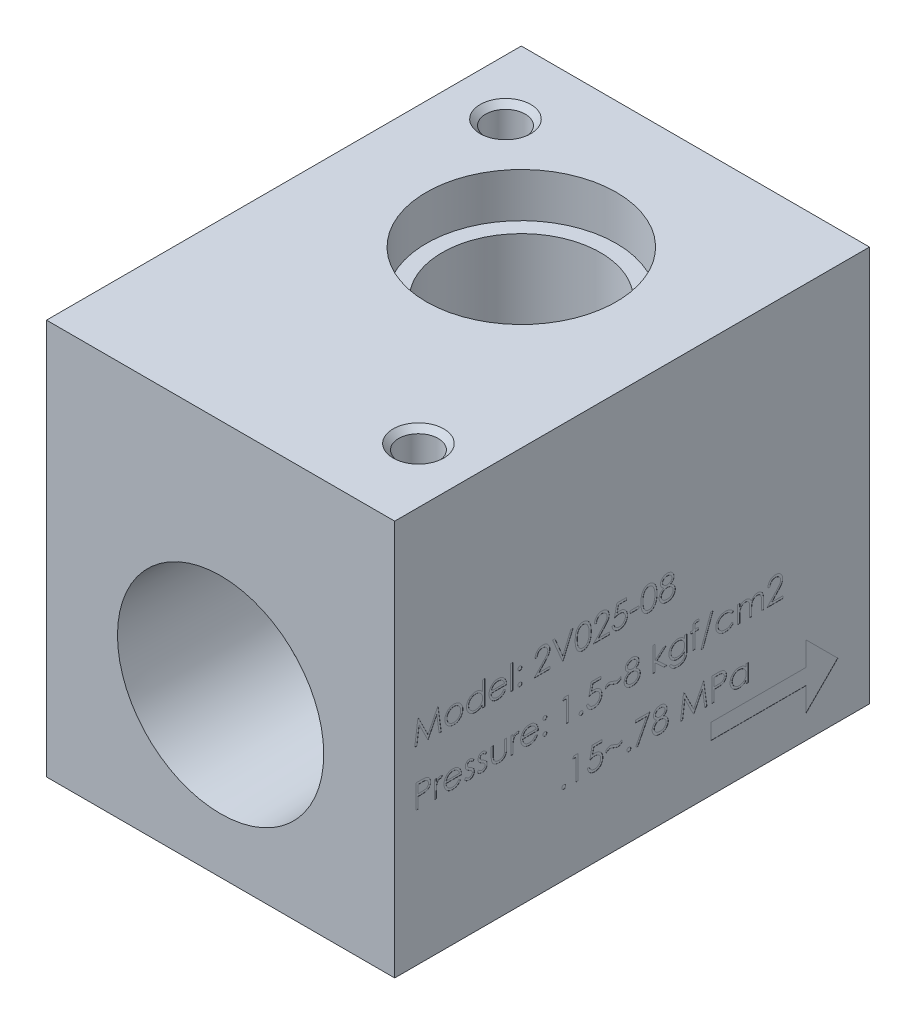
SolidWorks part; units mm, degrees
material "6061-T6 (SS)"
ref_plane "Front Plane" through (0, 0, 0) normal (0, 0, 1) x (1, 0, 0)
ref_plane "Top Plane" through (0, 0, 0) normal (0, 1, 0) x (1, 0, 0)
ref_plane "Right Plane" through (0, 0, 0) normal (1, 0, 0) x (0, 0, -1)
sketch "BaseS" plane through (0, 0, 0) normal (0, 1, 0) x (1, 0, 0)
  line L1 (-11, 15) -> (11, 15)
  line L2 (-11, 15) -> (-11, -15)
  line L3 (-11, -15) -> (11, -15)
  line L4 (11, 15) -> (11, -15)
  line L5 (-11, 15) -> (11, -15) construction
  line L6 (-11, -15) -> (11, 15) construction
  point P0 (0, 0)
  dimension "D1" = 22
  dimension "D2" = 30
extrude "BASE" add sketch "BaseS" along normal blind 25
sketch "TopBoreS" plane through (0, 25, 0) normal (0, 1, 0) x (1, 0, 0)
  line L0 (0, 15) -> (0, 4) construction
  line L2 (11, 15) -> (-11, 15) construction
  circle A0 centre (0, 4) radius 6
  dimension "D2" = 12
  dimension "D1" = 11
extrude "TOP BORE" cut sketch "TopBoreS" against normal blind 2.8
sketch "TopDeepBoreS" plane through (0, 22.2, 0) normal (0, 1, 0) x (1, 0, 0)
  circle A0 centre (0, 4) radius 5
  circle A1 centre (0, 4) radius 6 construction
  dimension "D1" = 1
  dimension "D2" = 10
extrude "TOP DEEP BORE" cut sketch "TopDeepBoreS" against normal offset from surface (6.2 mm away) 9 up to face at (0, 25, 2)
hole_wizard "M3x0.5 Tapped Hole1" positions "Sketch4" profile "Sketch5" tap size "M3x0.5" standard "ANSI Metric"
sketch "Sketch4" plane through (0, 25, 0) normal (0, 1, 0) x (1, 0, 0)
  line L0 (-11, -15) -> (11, -15) construction
  line L1 (11, -15) -> (11, 15) construction
  line L2 (-11, 15) -> (-11, -15) construction
  line L3 (11, 15) -> (-11, 15) construction
  point P0 (7.5, -10)
  point P7 (-7.5, 10.5)
  dimension "D1" = 5
  dimension "D2" = 3.5
  dimension "D3" = 3.5
  dimension "D4" = 4.5
  dimension "D5" = 15
  dimension "D6" = 20.5
sketch "Sketch5" plane through (7.5, 25, 10) normal (1, 0, 0) x (0, 0, 1)
  line L0 (0, 0) -> (0, 6.7511)
  line L1 (0, 6.7511) -> (1.25, 6)
  line L2 (1.25, 6) -> (1.25, 0.35)
  line L3 (1.25, 0.35) -> (1.6, 0)
  line L5 (1.6, 0) -> (0, 0)
  line L6 (-1.25, 0.35) -> (-1.6, 0) construction
  line L10 (0, 6.7511) -> (-1.25, 6) construction
  line L11 (0, -6.35) -> (0, 107.95) construction
  dimension "Tap Drill Dia." = 2.5
  dimension "Tap Drill Depth" = 6
  dimension "Near C'Sink Dia." = 3.2
  dimension "Near C'Sink Angle" = 90
  dimension "Drill Angle" = 118
cosmetic thread "Hole Thread1" parameters "D1"=4, "D2"=3
cosmetic thread "Hole Thread2" parameters "D1"=4, "D2"=3
hole_wizard "M3x0.5 Tapped Hole2" positions "Sketch12" profile "Sketch13" tap size "M3x0.5" standard "ANSI Metric"
sketch "Sketch12" plane through (0, 0, 0) normal (0, -1, 0) x (-1, 0, 0)
  line L1 (11, 15) -> (11, -15) construction
  line L2 (11, -15) -> (-11, -15) construction
  point P0 (7.5, -10.5)
  dimension "D1" = 4.5
  dimension "D2" = 3.5
sketch "Sketch13" plane through (-7.5, 0, 10.5) normal (1, 0, 0) x (0, 0, -1)
  line L0 (0, 0) -> (0, 8.2511)
  line L1 (0, 8.2511) -> (1.25, 7.5)
  line L2 (1.25, 7.5) -> (1.25, 0)
  line L5 (1.25, 0) -> (0, 0)
  line L10 (0, 8.2511) -> (-1.25, 7.5) construction
  line L11 (0, -6.35) -> (0, 107.95) construction
  dimension "Tap Drill Dia." = 2.5
  dimension "Tap Drill Depth" = 7.5
  dimension "Drill Angle" = 118
cosmetic thread "Hole Thread3" parameters "D1"=6, "D2"=3
sketch "LeftFittingVerticalReference" plane through (0, 0, 15) normal (0, 0, 1) x (1, 0, 0)
  line L0 (0, 0) -> (0, 10) construction
  line L1 (-11, 0) -> (11, 0) construction
  dimension "D1" = 10
sketch "RightFittingVerticalReference" plane through (0, 0, -15) normal (0, 0, -1) x (-1, 0, 0)
  line L0 (0, 0) -> (0, 9) construction
  dimension "D1" = 9
hole_wizard "1/4 Rc Tapped Hole1" positions "Sketch8" profile "Sketch9" size "1/4" standard "ISO"
sketch "Sketch8" plane through (0, 0, 15) normal (0, 0, 1) x (1, 0, 0)
  point P0 (0, 10)
sketch "Sketch9" plane through (0, 10, 15) normal (1, 0, 0) x (0, -1, 0)
  line L0 (0, 0) -> (0, 15.2146)
  line L1 (5.35, 12) -> (0, 15.2146)
  line L2 (-5.35, 12) -> (0, 15.2146) construction
  line L3 (5.35, 12) -> (5.35, 9)
  line L4 (5.35, 9) -> (6.2351, 9)
  line L5 (6.2351, 9) -> (6.5161, 0)
  line L6 (-6.2351, 9) -> (-6.5161, 0) construction
  line L7 (6.5161, 0) -> (0, 0)
  line L8 (0, -6.35) -> (0, 107.95) construction
  line L11 (-5.35, 9) -> (-6.2351, 9) construction
  dimension "Tap Drill Dia." = 10.7
  dimension "Tap Drill Depth" = 12
  dimension "Thread Dia." = 13.0321
  dimension "Thread Angle" = 3.576
  dimension "Thread Depth" = 9
  dimension "Drill Angle" = 118
hole_wizard "1/4 Rc Tapped Hole2" positions "Sketch10" profile "Sketch11" size "1/4" standard "ISO"
sketch "Sketch10" plane through (0, 0, -15) normal (0, 0, -1) x (-1, 0, 0)
  point P0 (0, 9)
sketch "Sketch11" plane through (0, 9, -15) normal (1, 0, 0) x (0, 1, 0)
  line L0 (0, 0) -> (0, 15.2146)
  line L1 (5.35, 12) -> (0, 15.2146)
  line L2 (-5.35, 12) -> (0, 15.2146) construction
  line L3 (5.35, 12) -> (5.35, 9)
  line L4 (5.35, 9) -> (6.2351, 9)
  line L5 (6.2351, 9) -> (6.5161, 0)
  line L6 (-6.2351, 9) -> (-6.5161, 0) construction
  line L7 (6.5161, 0) -> (0, 0)
  line L8 (0, -6.35) -> (0, 107.95) construction
  line L11 (-5.35, 9) -> (-6.2351, 9) construction
  dimension "Tap Drill Dia." = 10.7
  dimension "Tap Drill Depth" = 12
  dimension "Thread Dia." = 13.0321
  dimension "Thread Angle" = 3.576
  dimension "Thread Depth" = 9
  dimension "Drill Angle" = 118
mirror "Mirror1" about plane through (0, 0, 0) normal (1, 0, 0) of "M3x0.5 Tapped Hole2"
sketch "LeftFittingFillerS" plane through (0, 0, 0) normal (1, 0, 0) x (0, 0, -1)
  line L0 (-3, 15.35) -> (0.2146, 10)
  line L1 (-3, 15.35) -> (-3, 10)
  line L2 (-3, 15.35) -> (-3, 4.65) construction
  line L3 (-3, 10) -> (0.2146, 10)
revolve "LEFT FITTING FILLER" add sketch "LeftFittingFillerS" angle 360 about L3
sketch "RightFittingFillerS" plane through (0, 0, 0) normal (1, 0, 0) x (0, 0, -1)
  line L0 (3, 14.35) -> (-0.2146, 9)
  line L1 (-0.2146, 9) -> (3, 9)
  line L2 (3, 9) -> (3, 14.35)
revolve "RIGHT FITTING FILLER" add sketch "RightFittingFillerS" angle 360 about L1
hole_wizard "Ø2.5 (2.5) Diameter Hole1" positions "Sketch19" profile "Sketch20" hole size "Ø2.5" standard "ISO"
sketch "Sketch19" plane through (0, 16, 0) normal (0, 1, 0) x (1, 0, 0)
  circle A0 centre (0, 4) radius 5 construction
  point P0 (0, 4)
sketch "Sketch20" plane through (0, 16, -4) normal (1, 0, 0) x (0, 0, 1)
  line L0 (0, 0) -> (0, 2.7511)
  line L1 (0, 2.7511) -> (1.25, 2)
  line L2 (1.25, 2) -> (1.25, 0)
  line L5 (1.25, 0) -> (0, 0)
  line L10 (0, 2.7511) -> (-1.25, 2) construction
  line L11 (0, -6.35) -> (0, 107.95) construction
  dimension "Hole Dia." = 2.5
  dimension "Hole Depth" = 2
  dimension "Drill Angle" = 118
hole_wizard "Ø4.5 (4.5) Diameter Hole1" positions "Sketch29" profile "Sketch30" hole size "Ø4.5" standard "ISO"
sketch "Sketch29" plane through (0, 0, 3) normal (0, 0, -1) x (-1, 0, 0)
  point P0 (0, 9)
sketch "Sketch30" plane through (0, 9, 3) normal (1, 0, 0) x (0, -1, 0)
  line L0 (0, 0) -> (0, 5.3519)
  line L1 (0, 5.3519) -> (2.25, 4)
  line L2 (2.25, 4) -> (2.25, 0)
  line L5 (2.25, 0) -> (0, 0)
  line L10 (0, 5.3519) -> (-2.25, 4) construction
  line L11 (0, -6.35) -> (0, 107.95) construction
  dimension "Hole Dia." = 4.5
  dimension "Hole Depth" = 4
  dimension "Drill Angle" = 118
hole_wizard "Ø2.8 (2.8) Diameter Hole1" positions "ExitOrificeDiameterReferenceSketch" profile "ExitOrificeSketch" hole size "Ø2.8" standard "ISO"
sketch "ExitOrificeDiameterReferenceSketch" plane through (0, 16, 0) normal (0, 1, 0) x (1, 0, 0)
  line L0 (0, 0.4) -> (0, 4) construction
  circle A0 centre (0, 0.4) radius 1.4
  circle A2 centre (0, 4) radius 5 construction
  point P0 (0, 0.4)
  dimension "D1" = 2.8
sketch "ExitOrificeSketch" plane through (0, 16, -0.4) normal (1, 0, 0) x (0, 0, 1)
  line L0 (0, 0) -> (0, 6.8412)
  line L1 (0, 6.8412) -> (1.4, 6)
  line L2 (1.4, 6) -> (1.4, 0)
  line L5 (1.4, 0) -> (0, 0)
  line L10 (0, 6.8412) -> (-1.4, 6) construction
  line L11 (0, 0) -> (0, 107.95) construction
  dimension "Hole Dia." = 2.8
  dimension "Hole Depth" = 6
  dimension "Drill Angle" = 118
sketch "SolenoidInterfaceOrificeS" plane through (0, 0, 0) normal (1, 0, 0) x (0, 0, -1)
  line L0 (6, 16) -> (5.25, 16)
  line L1 (5.25, 16) -> (5.25, 17)
  line L2 (5.25, 17) -> (5.5, 17)
  line L3 (5.5, 17) -> (6, 16)
  line L6 (4, 16) -> (4, 22.2) construction
  dimension "D1" = 2
  dimension "D2" = 1.5
  dimension "D3" = 1
revolve "SOLENOID INTERFACE ORIFICE" add sketch "SolenoidInterfaceOrificeS" angle 360 about axis through (0, -7.1421, -4) along (0, 1, 0)
sketch "PartNameS" plane through (11, 0, 0) normal (1, 0, 0) x (0, 0, -1)
  line L0 (-15, 12) -> (15, 12) construction
  line L1 (-15, 25) -> (-15, 0) construction
  line L2 (15, 25) -> (15, 0) construction
  line L3 (-15, 0) -> (15, 0) construction
  text T0 "  Model: 2V025-08\r\n  Pressure: 1.5~8 kgf/cm2\r\n                  .15~.78 MPa\r\n" font "Century Gothic" height 1.5
  dimension "D1" = 12
extrude "PART NAME" cut sketch "PartNameS" against normal blind 0.01
sketch "FlowDirectionArrowS" plane through (11, 0, 0) normal (1, 0, 0) x (0, 0, -1)
  line L2 (11, 4) -> (5, 4)
  line L3 (5, 4) -> (5, 3)
  line L4 (5, 3) -> (11, 3)
  line L5 (11, 3) -> (11, 1.5)
  line L7 (5, 3.5) -> (13, 3.5) construction
  line L8 (11, 1.5) -> (13, 3.5)
  line L9 (11, 5.5) -> (13, 3.5)
  line L10 (11, 4) -> (11, 5.5)
  line L11 (-15, 0) -> (15, 0) construction
  line L12 (15, 0) -> (15, 9) construction
  point P1 (23.19, -0.5)
  point P8 (0, 0)
  point P9 (5.9116, 3.6413)
  dimension "TailLength" = 6
  dimension "TailWidth" = 1
  dimension "HeadLength" = 2
  dimension "HeadAngle" = 45
  dimension "YDim" = 3
  dimension "XDim" = 2
extrude "Cut-Extrude1" cut sketch "FlowDirectionArrowS" against normal up to surface (0.01 mm away) up to face at (10.99, 5.6485, -3.8942)
equation "\"D1@ExitOrificeDiameterReferenceSketch\" = \"Hole Dia.@ExitOrificeSketch\""
